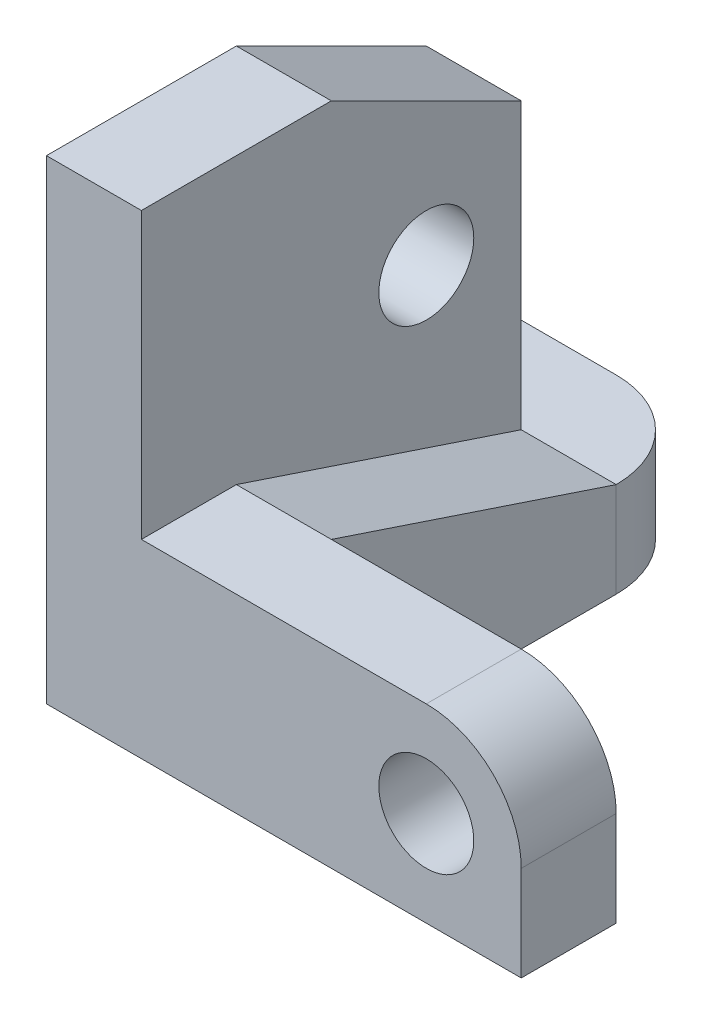
SolidWorks part; units mm, degrees
ref_plane "Front Plane" through (0, 0, 0) normal (0, 0, 1) x (1, 0, 0)
ref_plane "Top Plane" through (0, 0, 0) normal (0, 1, 0) x (1, 0, 0)
ref_plane "Right Plane" through (0, 0, 0) normal (1, 0, 0) x (0, 0, -1)
sketch "Sketch1" plane through (0, 0, 0) normal (1, 0, 0) x (0, 0, -1)
  line L0 (-30, 20) -> (-10, 20)
  line L1 (-10, 20) -> (10, 10)
  line L2 (10, 10) -> (10, -30)
  line L3 (10, -30) -> (-30, -30)
  line L4 (-30, -30) -> (-30, 20)
  line L5 (-30, -10) -> (-20, -10)
  line L6 (-20, -10) -> (-20, -30)
  line L7 (10, -20) -> (20, -20)
  line L8 (20, -20) -> (20, -30)
  line L9 (20, -30) -> (10, -30)
  line L10 (-20, -10) -> (10, -20)
  circle A0 centre (0, 0) radius 5
  dimension "D1" = 10
  dimension "D2" = 50
  dimension "D3" = 20
  dimension "D4" = 20
  dimension "D5" = 10
  dimension "D6" = 30
  dimension "D7" = 10
  dimension "D8" = 10
  dimension "D9" = 10
  dimension "D10" = 50
  dimension "D11" = 0
  dimension "D12" = 10
extrude "Boss-Extrude1" add sketch "Sketch1" along normal blind 50 contours L6 L5 L4 L3 region at (0, -20, 25)
extrude "Boss-Extrude2" add sketch "Sketch1<3>" along normal blind 20 contours L10 L6 L3 L2 | L9 L8 L7 L2 region at (0, -22.2222, 6.6667) region at (0, -25, -15)
sketch "Sketch1<3>" plane through (0, 0, 0) normal (1, 0, 0) x (0, 0, -1) same geometry as "Sketch1"
extrude "Boss-Extrude3" add sketch "Sketch1<4>" along normal blind 10 contours L5 L10 L2 L1 L0 L4 A0 region at (0, 1.9918, 10.5282)
sketch "Sketch1<4>" plane through (0, 0, 0) normal (1, 0, 0) x (0, 0, -1) same geometry as "Sketch1"
fillet "Fillet1" radius 10 2 edges at (50, -10, 25) (20, -25, -20)
sketch "Sketch2" plane through (0, 0, 20) normal (0, 0, -1) x (-1, 0, 0)
  line L0 (-50, -30) -> (-20, -30) construction
  circle A0 centre (-40, -20) radius 5
  dimension "D1" = 10
  dimension "D2" = 10
  dimension "D3" = 10
extrude "Cut-Extrude1" cut sketch "Sketch2" against normal blind 10
